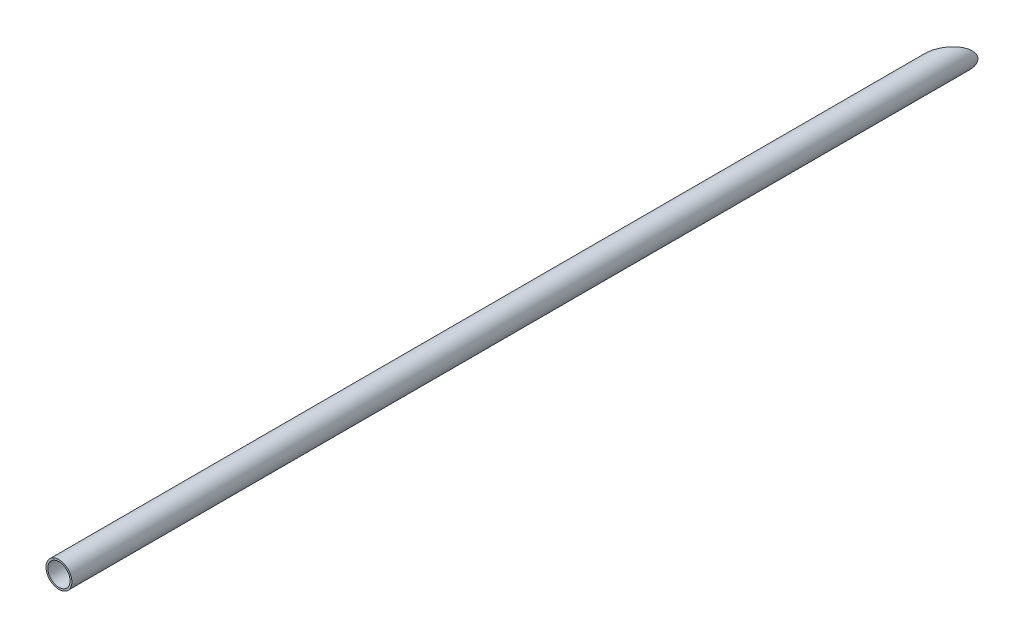
SolidWorks part; units mm, degrees
ref_plane "Front Plane" through (0, 0, 0) normal (0, 0, 1) x (1, 0, 0)
ref_plane "Top Plane" through (0, 0, 0) normal (0, 1, 0) x (1, 0, 0)
ref_plane "Right Plane" through (0, 0, 0) normal (1, 0, 0) x (0, 0, -1)
sketch "Sketch1" plane through (0, 0, 0) normal (0, 0, 1) x (1, 0, 0)
  circle A0 centre (0, 0) radius 12.7
  circle A1 centre (0, 0) radius 10.922
  dimension "D1" = 25.4
  dimension "D2" = 1.778
extrude "Boss-Extrude1" add sketch "Sketch1" along normal blind 889
ref_axis "Axis1" through (0, 0, 889) along (0, 0, -1)
sketch "Sketch3" plane through (0, 0, 0) normal (0, 1, 0) x (1, 0, 0)
  line L0 (0, 0) -> (12.7, 0)
  line L1 (12.7, 0) -> (-50.8, -90.6874)
  line L2 (12.7, -889) -> (12.7, 0) construction
  line L3 (0, 0) -> (-50.8, 0)
  line L4 (-50.8, 0) -> (-50.8, -90.6874)
  line L5 (0, -889) -> (0, 0) construction
  point P3 (0, -18.1375)
  dimension "D1" = 55
  dimension "D2" = 63.5
extrude "Cut-Extrude1" cut sketch "Sketch3" against normal through all both and the other way through all
